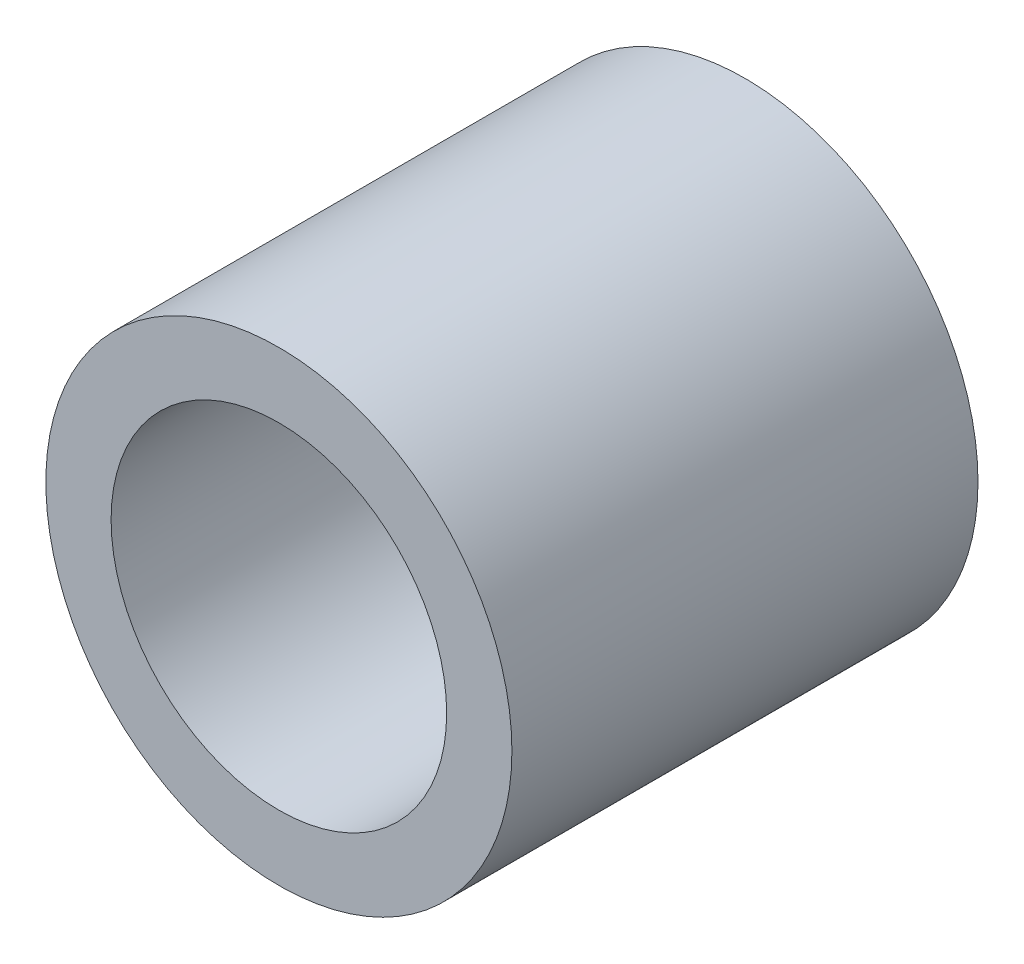
SolidWorks part; units mm, degrees
material "Nylon 101"
ref_plane "Front Plane" through (0, 0, 0) normal (0, 0, 1) x (1, 0, 0)
ref_plane "Top Plane" through (0, 0, 0) normal (0, 1, 0) x (1, 0, 0)
ref_plane "Right Plane" through (0, 0, 0) normal (1, 0, 0) x (0, 0, -1)
sketch "Sketch1" plane through (0, 0, 0) normal (0, 0, 1) x (1, 0, 0)
  circle A0 centre (0, 0) radius 1.5875
  circle A1 centre (0, 0) radius 1.143
  dimension "OD" = 3.175
  dimension "ID" = 2.286
extrude "Extrude1" add sketch "Sketch1" along normal mid plane 3.175
sketch "Sketch2" plane through (0, 0, 0) normal (1, 0, 0) x (0, 0, -1)
  line L0 (-1.5875, -1.143) -> (1.5875, -1.143) construction
  line L3 (1.5875, 1.143) -> (-1.5875, 1.143) construction
  line L5 (-1.5875, -1.143) -> (1.5875, -1.143)
  line L6 (1.5875, 1.143) -> (-1.5875, 1.143)
sketch "Sketch4" plane through (0, 0, 1.5875) normal (0, 0, 1) x (1, 0, 0)
  line L0 (0, 0) -> (-0.8082, 0.8082)
  line L1 (0, -5.2388) -> (0, 5.2388) construction
  circle A0 centre (0, 0) radius 1.143 construction
  dimension "D1" = 45
